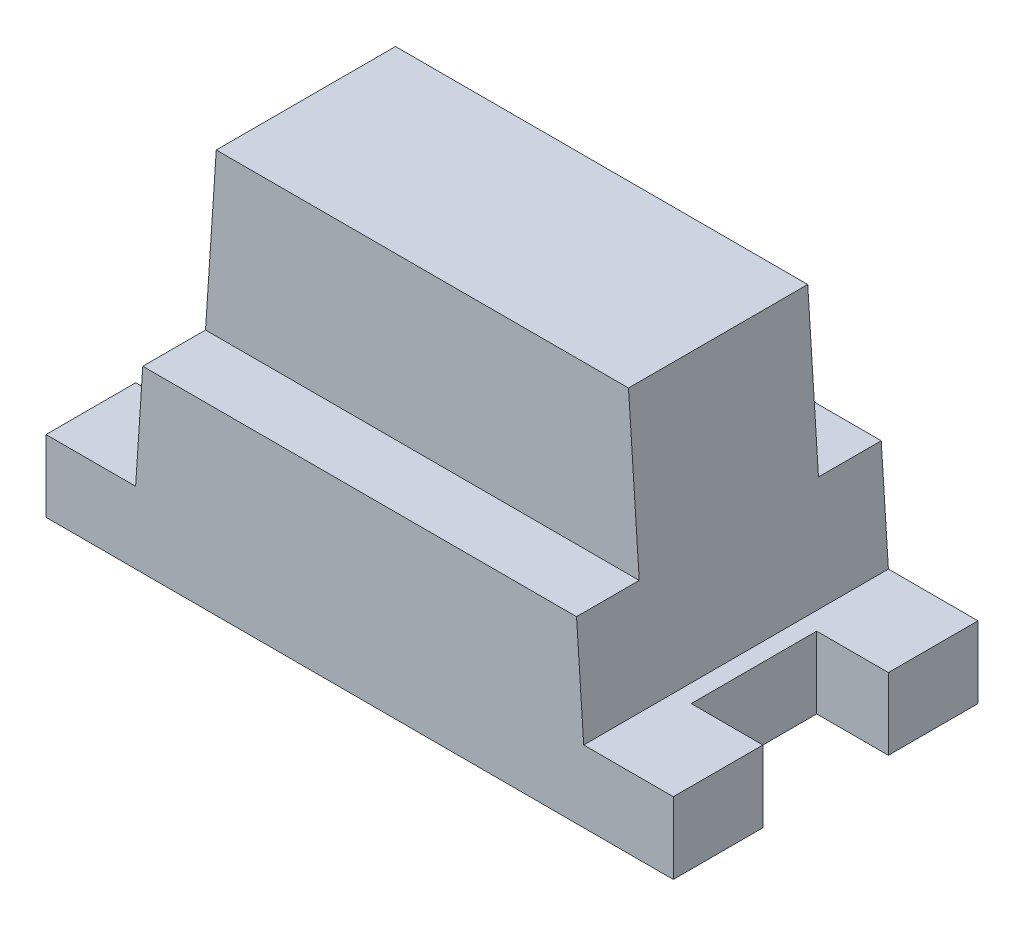
SolidWorks part; units mm, degrees
ref_plane "Front Plane" through (0, 0, 0) normal (0, 0, 1) x (1, 0, 0)
ref_plane "Top Plane" through (0, 0, 0) normal (0, 1, 0) x (1, 0, 0)
ref_plane "Right Plane" through (0, 0, 0) normal (1, 0, 0) x (0, 0, -1)
sketch "Sketch1" plane through (0, 0, 0) normal (0, 0, 1) x (1, 0, 0)
  line L0 (-38.6631, -22.6824) -> (-48.6631, -22.6824)
  line L4 (21.3369, -22.6824) -> (11.3369, -22.6824)
  line L5 (-48.6631, -30.6824) -> (21.3369, -30.6824)
  line L7 (-36.6631, 7.3176) -> (9.3369, 7.3176)
  line L8 (-48.6631, -30.6824) -> (-48.6631, -22.6824)
  line L9 (-38.6631, -22.6824) -> (-36.6631, 7.3176)
  line L10 (11.3369, -22.6824) -> (9.3369, 7.3176)
  line L12 (-37.8631, -10.6824) -> (10.5369, -10.6824)
  line L13 (21.3369, -30.6824) -> (21.3369, -22.6824)
  point P1 (0, 0)
  point P3 (0, 0)
  point P5 (0, 0)
extrude "Boss-Extrude1" add sketch "Sketch1" along normal blind 17 and the other way blind 17 contours L5 L13 L4 L10 L12 L9 L0 L8 region at (-13.6631, -21.5669, 0)
extrude "Boss-Extrude2" add sketch "Sketch1<3>" along normal blind 10 and the other way blind 10 contours L9 L12 L10 L7 region at (-13.6631, -1.7586, 0)
sketch "Sketch1<3>" plane through (0, 0, 0) normal (0, 0, 1) x (1, 0, 0) same geometry as "Sketch1"
sketch "Sketch3" plane through (21.3369, 0, 0) normal (1, 0, 0) x (0, 0, -1)
  line L0 (17, -30.6824) -> (-17, -30.6824) construction
  line L1 (-7, -30.6824) -> (7, -30.6824)
  line L2 (-7, -30.6824) -> (-7, -22.6824)
  line L3 (-7, -22.6824) -> (7, -22.6824)
  line L4 (7, -30.6824) -> (7, -22.6824)
  line L5 (17, -22.6824) -> (-17, -22.6824) construction
  line L6 (-17, -30.6824) -> (-17, -22.6824) construction
  dimension "D1" = 14
  dimension "D2" = 10
extrude "Cut-Extrude1" cut sketch "Sketch3" against normal blind 8
sketch3d "3DSketch2"
  point P0 (-48.6631, -28.2517, -11.8777)
sketch "Sketch4" plane through (-48.6631, 0, 0) normal (-1, 0, 0) x (0, 0, 1)
  line L0 (-17, -22.6824) -> (17, -22.6824) construction
  line L1 (-7, -22.6824) -> (7, -22.6824)
  line L2 (-7, -22.6824) -> (-7, -30.6824)
  line L3 (-7, -30.6824) -> (7, -30.6824)
  line L4 (7, -22.6824) -> (7, -30.6824)
  line L5 (-17, -30.6824) -> (17, -30.6824) construction
  line L6 (-17, -30.6824) -> (-17, -22.6824) construction
  dimension "D1" = 14
  dimension "D2" = 10
extrude "Cut-Extrude2" cut sketch "Sketch4" against normal blind 8
